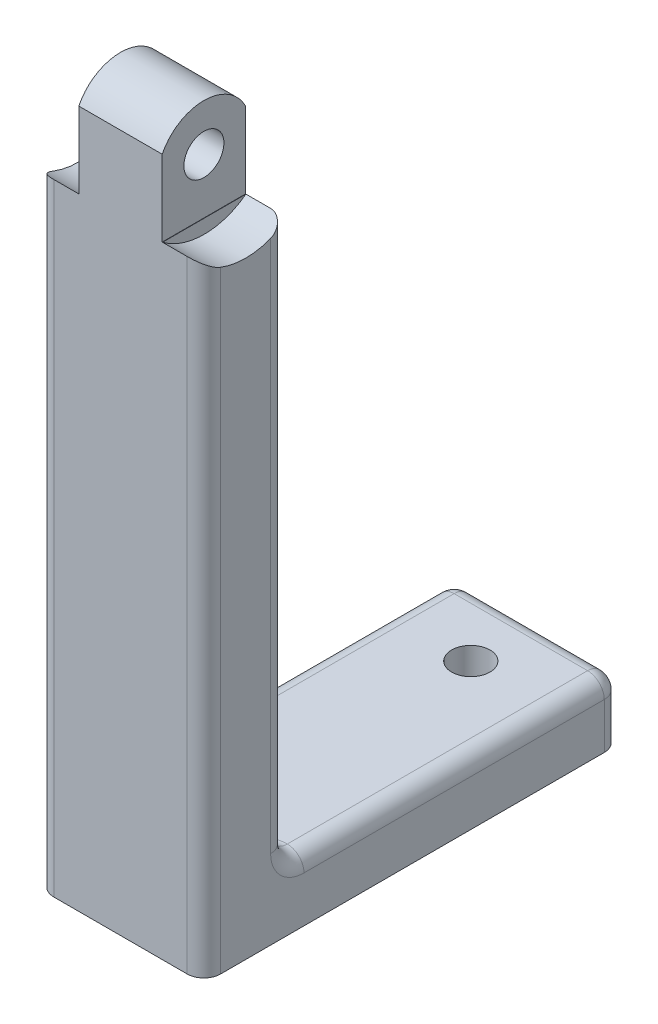
SolidWorks part; units mm, degrees
ref_plane "Front Plane" through (0, 0, 0) normal (0, 0, 1) x (1, 0, 0)
ref_plane "Top Plane" through (0, 0, 0) normal (0, 1, 0) x (1, 0, 0)
ref_plane "Right Plane" through (0, 0, 0) normal (1, 0, 0) x (0, 0, -1)
sketch "Sketch3" plane through (0, 0, 0) normal (1, 0, 0) x (0, 0, -1)
  line L0 (0, 0) -> (31.75, 0)
  line L1 (31.75, 0) -> (31.75, 4.7625)
  line L2 (31.75, 4.7625) -> (6.35, 4.7625)
  line L3 (6.35, 4.7625) -> (6.35, 55.5625)
  line L4 (6.35, 55.5625) -> (0, 55.5625)
  line L5 (0, 55.5625) -> (0, 0)
  dimension "D1" = 31.75
  dimension "D2" = 4.7625
  dimension "D3" = 6.35
  dimension "D4" = 50.8
extrude "Boss-Extrude1" add sketch "Sketch3" along normal blind 12.7
sketch "Sketch4" plane through (0, 4.7625, 0) normal (0, 1, 0) x (1, 0, 0)
  line L0 (6.35, 31.75) -> (6.35, 0) construction
  line L1 (12.7, 31.75) -> (0, 31.75) construction
  line L2 (12.7, 0) -> (0, 0) construction
  circle A0 centre (6.35, 26.67) radius 1.4605
  circle A7 centre (6.35, 7.874) radius 1.4605
  dimension "D1" = 26.67
  dimension "D3" = 2.921
  dimension "D2" = 7.874
extrude "Cut-Extrude1" cut sketch "Sketch4" against normal through all
sketch "Sketch7" plane through (0, 0, -6.35) normal (0, 0, -1) x (-1, 0, 0)
  line L1 (-12.7, 55.5625) -> (-9.525, 55.5625)
  line L2 (-12.7, 55.5625) -> (-12.7, 47.3075)
  line L3 (-12.7, 4.7625) -> (-12.7, 55.5625) construction
  line L4 (-9.525, 55.5625) -> (-9.525, 47.3075)
  line L6 (0, 55.5625) -> (-3.175, 55.5625)
  line L7 (0, 55.5625) -> (0, 47.3075)
  line L8 (0, 4.7625) -> (0, 55.5625) construction
  line L9 (-3.175, 55.5625) -> (-3.175, 47.3075)
  line L10 (-12.7, 47.3075) -> (-9.525, 47.3075)
  line L11 (-3.175, 47.3075) -> (0, 47.3075)
  dimension "D1" = 3.175
  dimension "D2" = 8.255
extrude "Cut-Extrude3" cut sketch "Sketch7" against normal through all
sketch "Sketch8" plane through (9.525, 0, 0) normal (1, 0, 0) x (0, 0, -1)
  line L0 (0, 55.5625) -> (6.35, 55.5625) construction
  line L2 (3.175, 55.5625) -> (3.175, 47.3075) construction
  line L3 (0, 47.3075) -> (6.35, 47.3075) construction
  circle A0 centre (3.175, 51.4985) radius 1.524
  dimension "D1" = 3.048
  dimension "D2" = 4.064
extrude "Cut-Extrude4" cut sketch "Sketch8" against normal blind 12.7
sketch "Sketch9" plane through (12.7, 0, 0) normal (1, 0, 0) x (0, 0, -1)
  line L0 (6.35, 4.7625) -> (6.35, 47.3075) construction
  line L1 (0, 47.3075) -> (6.35, 47.3075)
  arc A0 (0, 47.3075) -> (6.35, 47.3075) centre (3.175, 51.4985) ccw
extrude "Cut-Extrude5" cut sketch "Sketch9" against normal blind 3.1496
ref_plane "Plane1" through (6.35, 0, 0) normal (1, 0, 0) x (0, 0, -1)
mirror "Mirror1" about plane through (6.35, 0, 0) normal (1, 0, 0) of "Cut-Extrude5"
sketch "Sketch10" plane through (9.525, 0, 0) normal (1, 0, 0) x (0, 0, -1)
  line L0 (0, 47.3075) -> (0, 55.5625) construction
  line L1 (6.35, 47.3075) -> (6.35, 55.5625) construction
  line L2 (0, 53.0999) -> (0, 55.6399)
  line L3 (0, 55.6399) -> (6.35, 55.6399)
  line L4 (6.35, 55.6399) -> (6.35, 53.0999)
  arc A0 (0, 53.0999) -> (6.35, 53.0999) centre (3.175, 51.4985) cw
  dimension "D2" = 3.556
  dimension "D1" = 2.54
extrude "Cut-Extrude6" cut sketch "Sketch10" against normal through all
sketch "Sketch11" plane through (0, 0, -6.35) normal (0, 0, -1) x (-1, 0, 0)
  line L0 (-6.35, 23.8125) -> (-10.16, 23.8125)
  line L1 (-6.35, 17.4625) -> (-6.35, -17.4625) construction
  line L2 (-10.16, 23.8125) -> (-10.16, 4.7625)
  line L3 (-12.7, 4.7625) -> (0, 4.7625) construction
  line L4 (-10.16, 4.7625) -> (-2.54, 4.7625)
  line L5 (-2.54, 4.7625) -> (-2.54, 23.8125)
  line L6 (-2.54, 23.8125) -> (-6.35, 23.8125)
  dimension "D1" = 3.81
  dimension "D2" = 19.05
extrude "Cut-Extrude7" cut sketch "Sketch11" against normal blind 3.81
fillet "Fillet2" radius 1.27 18 edges at (0, 26.035, -6.35) (2.54, 4.7625, -4.445) (10.16, 4.7625, -4.445) (0, 23.6537, 0) (12.7, 23.6537, 0) (12.7, 2.3813, -31.75) (0, 2.3813, -31.75) (6.35, 4.7625, -31.75) (0, 4.7625, -19.05) (6.35, 4.7625, -2.54) (10.16, 14.2875, -2.54) (2.54, 14.2875, -2.54) (6.35, 23.8125, -2.54) (10.16, 14.2875, -6.35) (2.54, 14.2875, -6.35) (6.35, 23.8125, -6.35) (12.7, 4.7625, -19.05) (12.7, 26.035, -6.35)
